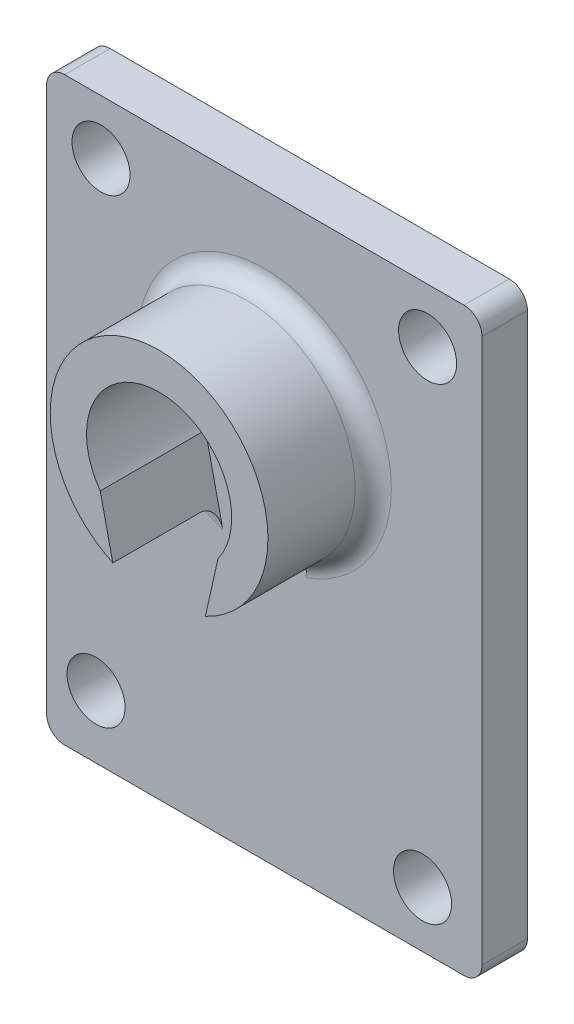
SolidWorks part; units mm, degrees
other "Marcação1"
sketch "Esboço4" plane through (-1.4022, -20.9776, 8.3) normal (-0.1528, -0.0621, 0.9863) x (0.9879, 0.0164, 0.1541)
ref_plane "Plano frontal" through (0, 0, 0) normal (0, 0, 1) x (1, 0, 0)
ref_plane "Plano superior" through (0, 0, 0) normal (0, 1, 0) x (1, 0, 0)
ref_plane "Plano direito" through (0, 0, 0) normal (1, 0, 0) x (0, 0, -1)
sketch "Esboço1" plane through (0, 0, 0) normal (0, 0, 1) x (1, 0, 0)
  line L0 (10.5978, 11.0224) -> (10.5978, -20.9776) construction
  line L1 (-1.4022, 11.0224) -> (22.5978, 11.0224)
  line L2 (-1.4022, 11.0224) -> (-1.4022, -20.9776)
  line L3 (-1.4022, -20.9776) -> (22.5978, -20.9776)
  line L4 (22.5978, 11.0224) -> (22.5978, -20.9776)
  line L5 (-1.4022, -4.7187) -> (22.5978, -4.9776) construction
  line L6 (-1.4022, -20.9776) -> (22.5978, 11.0224) construction
  circle A0 centre (1.5978, 8.0224) radius 1.6
  circle A1 centre (19.5978, 8.0224) radius 1.6
  circle A2 centre (19.318, -17.9098) radius 1.6
  circle A3 centre (1.3222, -17.5215) radius 1.6
  dimension "D3" = 3.2
  dimension "D1" = 24
  dimension "D2" = 32
  dimension "D4" = 3
  dimension "D5" = 3
extrude "Ressalto-extrusão1" add sketch "Esboço1" along normal blind 2.5
sketch "Esboço2" plane through (0, 0, 2.5) normal (0, 0, 1) x (1, 0, 0)
  line L0 (-1.4022, 6.2724) -> (22.5978, 6.2724) construction
  line L1 (-1.4022, 11.0224) -> (-1.4022, -20.9776) construction
  line L2 (22.5978, -20.9776) -> (22.5978, 11.0224) construction
  line L3 (22.5978, 11.0224) -> (-1.4022, 11.0224) construction
  line L4 (-1.4022, -8.2276) -> (22.5978, -8.2276) construction
  line L5 (16.5978, 11.0224) -> (16.5978, -20.9776) construction
  line L6 (-1.4022, -20.9776) -> (22.5978, -20.9776) construction
  line L7 (4.5978, 11.0224) -> (4.5978, -20.9776) construction
  line L8 (4.5978, -8.2276) -> (16.5978, -8.2276)
  line L9 (16.5978, -8.2276) -> (16.5978, 6.2724)
  line L10 (16.5978, 6.2724) -> (4.5978, 6.2724)
  line L11 (4.5978, 6.2724) -> (4.5978, -8.2276)
  line L12 (8.0478, -8.2276) -> (13.1478, -8.2276)
  line L13 (13.1478, -2.8094) -> (13.1478, -8.2276)
  line L14 (8.0478, -2.8094) -> (8.0478, -8.2276)
  circle A0 centre (10.5978, 0.2724) radius 6
  circle A1 centre (10.5978, 0.2724) radius 4
  point P23 (8.0478, -5.1587)
  point P24 (13.1478, -5.1587)
  dimension "D6" = 8
  dimension "D1" = 4.75
  dimension "D2" = 14.5
  dimension "D3" = 12
  dimension "D4" = 6
extrude "Ressalto-extrusão2" add sketch "Esboço2" along normal blind 5.8 contours A1 L13 A0 L14 region at (6.4723, 4.3979, 2.5)
sketch "Esboço3" plane through (0, 0, 8.3) normal (0, 0, 1) x (1, 0, 0)
  line L0 (10.5978, 6.2724) -> (10.5978, -5.7276) construction
  line L1 (13.1478, -5.1587) -> (13.8414, -2.0682)
  line L2 (13.1478, -5.1587) -> (13.1478, -2.8094)
  line L3 (8.0478, -5.1587) -> (8.0478, -2.8094)
  line L4 (8.0478, -5.1587) -> (7.3541, -2.0682)
  arc A0 (13.1478, -5.1587) -> (8.0478, -5.1587) centre (10.5978, 0.2724) ccw construction
  arc A1 (13.1478, -2.8094) -> (8.0478, -2.8094) centre (10.5978, 0.2724) ccw construction
  circle A2 centre (10.5978, 0.2724) radius 4
  arc A3 (13.1478, -2.8094) -> (8.0478, -2.8094) centre (10.5978, 0.2724) ccw construction
  arc M5 (8.0478, -2.8094) -> (13.1478, -2.8094) centre (10.5978, 0.2724) cw
  line M6 (13.1478, -2.8094) -> (13.1478, -5.1587)
  line M8 (8.0478, -5.1587) -> (8.0478, -2.8094)
extrude "Corte-extrusão1" cut sketch "Esboço3" against normal blind 5.8 contours L4 M8 M5 | L1 M6 M5 region at (13.3755, -3.3702, 8.3) region at (7.82, -3.3702, 8.3)
fillet "Filete1" radius 1 1 edges at (10.5978, 6.2724, 2.5)
fillet "Filete2" radius 1 4 edges at (-1.4022, 11.0224, 1.25) (-1.4022, -20.9776, 1.25) (22.5978, -20.9776, 1.25) (22.5978, 11.0224, 1.25)
